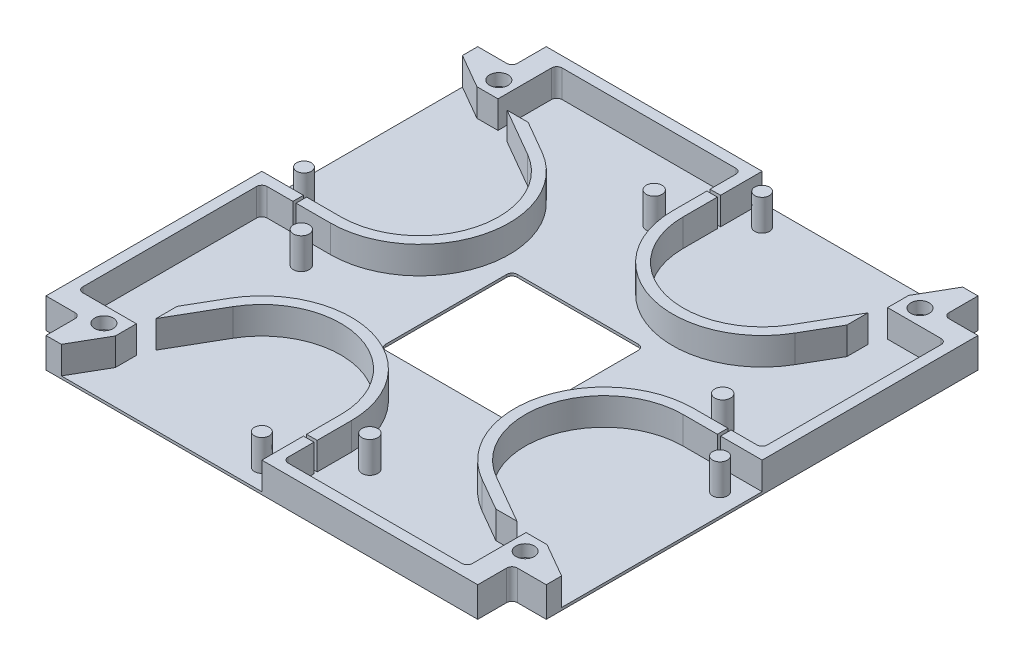
SolidWorks part; units mm, degrees
material "7075-T6 (SN)"
ref_plane "Front Plane" through (0, 0, 0) normal (0, 0, 1) x (1, 0, 0)
ref_plane "Top Plane" through (0, 0, 0) normal (0, 1, 0) x (1, 0, 0)
ref_plane "Right Plane" through (0, 0, 0) normal (1, 0, 0) x (0, 0, -1)
sketch "Sketch1" plane through (0, 0, 0) normal (0, 1, 0) x (1, 0, 0)
  line L0 (0, 0) -> (0, 6.51)
  line L21 (0, 6.51) -> (82, 6.51)
  line L22 (82, 6.51) -> (82, 0)
  line L23 (82, 0) -> (88.51, 0)
  line L24 (88.51, 0) -> (88.51, -82)
  line L25 (88.51, -82) -> (82, -82)
  line L26 (82, -82) -> (82, -88.51)
  line L27 (82, -88.51) -> (0, -88.51)
  line L28 (0, -88.51) -> (0, -82)
  line L29 (0, -82) -> (-6.51, -82)
  line L30 (-6.51, -82) -> (-6.51, 0)
  line L31 (-6.51, 0) -> (0, 0)
  dimension "D1" = 82
  dimension "D2" = 6.51
extrude "Boss-Extrude1" add sketch "Sketch1" along normal blind 0.5
sketch "Sketch2" plane through (0, 0.5, 0) normal (0, 1, 0) x (1, 0, 0)
  line L0 (-6.51, 0) -> (-6.51, -82) construction
  line L1 (0, 6.51) -> (41, 6.51)
  line L2 (0, 6.51) -> (0, 4.51)
  line L3 (0, 4.51) -> (41, 4.51)
  line L4 (41, 6.51) -> (41, 4.51)
  line L5 (88.51, 0) -> (86.51, 0)
  line L6 (88.51, 0) -> (88.51, -41)
  line L7 (88.51, -41) -> (86.51, -41)
  line L8 (86.51, 0) -> (86.51, -41)
  line L9 (82, -88.51) -> (41, -88.51)
  line L10 (82, -88.51) -> (82, -86.51)
  line L11 (82, -86.51) -> (41, -86.51)
  line L12 (41, -88.51) -> (41, -86.51)
  line L13 (-6.51, -82) -> (-4.51, -82)
  line L14 (-6.51, -82) -> (-6.51, -41)
  line L15 (-6.51, -41) -> (-4.51, -41)
  line L16 (-4.51, -82) -> (-4.51, -41)
  line L17 (-6.51, -82) -> (0, -82) construction
  line L18 (41, -8.49) -> (41, 24.5303) construction
  line L19 (56, 6.51) -> (0, 6.51) construction
  line L20 (82, 6.51) -> (0, 6.51) construction
  line L21 (79.094, 6.51) -> (75.3355, 0)
  line L22 (79.094, 6.51) -> (82, 6.51)
  line L23 (82, 6.51) -> (82, 0)
  line L24 (82, 0) -> (86.51, 0)
  line L25 (41, 4.51) -> (41, -8.49)
  line L26 (86.51, -4) -> (75.3355, -4)
  line L27 (39, 4.51) -> (39, -8.49)
  line L28 (72.9929, -8) -> (73.0261, -8)
  line L29 (74.3355, -10.7321) -> (70.7224, -16.99)
  line L31 (75.3355, -4) -> (75.3355, 0)
  line L32 (74.3355, -6.7321) -> (74.3355, -10.7321)
  line L33 (74.3355, -6.7321) -> (68.9904, -15.99)
  circle A0 centre (56, -8.49) radius 15
  circle A1 centre (56, -8.49) radius 17 construction
  arc A2 (70.7224, -16.99) -> (39, -8.49) centre (56, -8.49) cw
  line M24 (88.51, -82) -> (88.51, 0)
  line M25 (88.51, 0) -> (82, 0)
  line M26 (82, 0) -> (82, 6.51)
  line M27 (82, 6.51) -> (0, 6.51)
  line M28 (0, 6.51) -> (0, 0)
  dimension "D3" = 30
  dimension "D6" = 34
  dimension "D1" = 41
  dimension "D2" = 2
  dimension "D7" = 4
  dimension "D8" = 4
  dimension "D5" = 0
  dimension "D9" = 1
  dimension "D4" = 30
  dimension "D10" = 6.6645
  dimension "D11" = 30
  dimension "D12" = 4
extrude "Boss-Extrude2" add sketch "Sketch2" along normal blind 5.2 contours L4 L3 M27 M28 | A2 L28 A0 L25 L3 L27 | L8 L7 M25 M24 | L26 L8 M25 M26 M27 region at (80.332, 0.5, 0.0167) region at (20.5, 0.5, -5.51) region at (40.5365, 0.5, 1.99) region at (87.51, 0.5, 20.5)
sketch "Sketch3" [suppressed] plane through (0, 0.5, 0) normal (0, 1, 0) x (1, 0, 0)
  line L0 (35.5217, -6.4679) -> (39.51, -26.4679)
  line L1 (39.51, -26.4679) -> (39.51, -29.4679)
  line L2 (39.51, -29.4679) -> (79.51, -29.4679)
  line L3 (79.51, -29.4679) -> (79.51, -26.4679)
  line L4 (79.51, -26.4679) -> (83.4983, -6.4679)
  line L6 (35.5217, -6.4679) -> (39.5217, -6.4679)
  line L7 (83.4983, -6.4679) -> (79.4983, -6.4679)
  line L9 (89.51, -41) -> (89.51, 0) construction
  arc A0 (79.4983, -6.4679) -> (39.5217, -6.4679) centre (59.51, -5.7836) cw
  circle A1 centre (58.485, 0) radius 15 construction
  dimension "D3" = 20
  dimension "D7" = 30
  dimension "D1" = 3
  dimension "D2" = 4
  dimension "D4" = 20
  dimension "D5" = 40
  dimension "D6" = 10
extrude "Boss-Extrude3" [suppressed] add sketch "Sketch3" along normal blind 6
ref_plane "Plane1" through (41, 0, 41) normal (0.7071, 0, 0.7071) x (0.7071, 0, -0.7071)
ref_plane "Plane2" through (0, 0, 0) normal (0.7071, 0, -0.7071) x (-0.7071, 0, -0.7071)
ref_axis "Axis1" through (41, -0.325, 41) along (0, 1, 0)
pattern_circular "CirPattern1" count 4 every 90 about axis through (41, -0.325, 41) along (0, 1, 0) of "Boss-Extrude2"
sketch "Sketch4" plane through (0, 0, 0) normal (0, -1, 0) x (1, 0, 0)
  line L0 (78, -6.51) -> (78, -0.51) construction
  line L1 (82, -6.51) -> (0, -6.51) construction
  line L2 (82, 0) -> (82, -6.51) construction
  line L3 (88.51, 78) -> (82.51, 78) construction
  line L4 (88.51, 82) -> (88.51, 0) construction
  line L5 (4, 88.51) -> (4, 82.51) construction
  line L6 (0, 88.51) -> (82, 88.51) construction
  line L7 (-6.51, 4) -> (-0.51, 4) construction
  line L8 (-6.51, 0) -> (-6.51, 82) construction
  line L10 (82, 82) -> (88.51, 82) construction
  line L11 (0, 82) -> (0, 88.51) construction
  line L12 (0, 0) -> (-6.51, 0) construction
  point P7 (78, -0.51)
  dimension "D1" = 6
  dimension "D2" = 4
  dimension "D3" = 4
  dimension "D4" = 4
  dimension "D5" = 4
  dimension "D6" = 6
  dimension "D7" = 6
  dimension "D8" = 6
sketch "Sketch8" plane through (0, 0.5, 0) normal (0, 1, 0) x (1, 0, 0)
  line L0 (2.906, -88.51) -> (41, -88.51) construction
  line L1 (41, -88.51) -> (41, -73.51) construction
  circle A0 centre (37, -84.51) radius 1.4
  dimension "D1" = 2.8
  dimension "D2" = 4
  dimension "D3" = 4
extrude "Boss-Extrude4" add sketch "Sketch8" along normal blind 5.9
pattern_circular "CirPattern2" count 4 every 90 about axis through (41, -0.325, 41) along (0, 1, 0) of "Boss-Extrude4"
fillet "Fillet1" radius 1 8 edges at (-4.51, 3.1, 78) (-4.51, 3.1, 43) (4, 3.1, -4.51) (39, 3.1, -4.51) (86.51, 3.1, 4) (86.51, 3.1, 39) (78, 3.1, 86.51) (43, 3.1, 86.51)
sketch "Sketch11" plane through (0, 0.5, 0) normal (0, 1, 0) x (1, 0, 0)
  line L0 (53.5, -53.5) -> (53.5, -28.5)
  line L1 (53.5, -28.5) -> (28.5, -28.5)
  line L2 (28.5, -28.5) -> (28.5, -53.5)
  line L3 (28.5, -53.5) -> (53.5, -53.5)
  line L5 (79.094, 6.51) -> (41, 6.51) construction
  line L6 (-6.51, -2.906) -> (-6.51, -41) construction
  dimension "D1" = 25
  dimension "D2" = 25
  dimension "D3" = 35.01
  dimension "D4" = 35.01
extrude "Cut-Extrude2" cut sketch "Sketch11" against normal through all
sketch "Sketch14" plane through (0, 6.4, 0) normal (0, 1, 0) x (1, 0, 0)
  point P0 (37, -84.51)
sketch "Sketch15" plane through (0, 5.7, 0) normal (0, 1, 0) x (1, 0, 0)
  line L0 (82, -82) -> (88.51, -82) construction
  line L2 (78, -85.51) -> (78, -75.3355) construction
  circle A0 centre (81, -78.5) radius 0.9
  circle A1 centre (78.5, -1) radius 0.9
  circle A2 centre (1, -3.5) radius 0.9
  circle A3 centre (3.5, -81) radius 0.9
  point P0 (1, -3.5)
  point P1 (1, -3.5)
  point P2 (3.5, -81)
  point P3 (81, -78.5)
  point P4 (78.5, -1)
  point P5 (3.5, -81)
  dimension "D3" = 1.8
  dimension "D4" = 1.8
  dimension "D5" = 1.8
  dimension "D6" = 1.8
  dimension "D1" = 3.5
  dimension "D2" = 3
extrude "Cut-Extrude3" cut sketch "Sketch15" against normal through all
sketch "Sketch16" plane through (0, 5.7, 0) normal (0, 1, 0) x (1, 0, 0)
  circle A0 centre (78.5, -1) radius 1.75
  circle A1 centre (81, -78.5) radius 1.75
  circle A2 centre (3.5, -81) radius 1.75
  circle A3 centre (1, -3.5) radius 1.75
  dimension "D1" = 3.5
  dimension "D2" = 3.5
  dimension "D3" = 3.5
  dimension "D4" = 3.5
extrude "Cut-Extrude4" cut sketch "Sketch16" against normal blind 2.3
hole_wizard "CBORE for M1.6 SHCS2" positions "3DSketch2" profile "Sketch18" counterbore size "M1.6" standard "ANSI Metric" end condition through all
sketch3d "3DSketch2"
  line L0 (81, 0, 78.5) -> (81, 3.4, 78.5) construction
  line L1 (78.5, 0, 1) -> (78.5, 3.4, 1) construction
  line L2 (1, 0, 3.5) -> (1, 3.4, 3.5) construction
  line L3 (3.5, 0, 81) -> (3.5, 3.4, 81) construction
  point P0 (81, 0, 78.5)
  point P4 (78.5, 0, 1)
  point P8 (1, 0, 3.5)
  point P12 (3.5, 0, 81)
sketch "Sketch18" plane through (81, 0, 78.5) normal (1, 0, 0) x (0, 0, -1)
  line L0 (0, 0) -> (0, 6.4)
  line L1 (0, 6.4) -> (0.9, 6.4)
  line L3 (0.9, 6.4) -> (0.9, 1.6)
  line L4 (0.9, 1.6) -> (1.75, 1.6)
  line L5 (1.75, 1.6) -> (1.75, 0)
  line L7 (1.75, 0) -> (0, 0)
  line L11 (0, -6.35) -> (0, 107.95) construction
  dimension "Thru Hole Dia." = 1.8
  dimension "Thru Hole Depth" = 6.4
  dimension "C'Bore Dia." = 3.5
  dimension "C'Bore Depth" = 1.6
sketch "Sketch20" plane through (0, 5.7, 0) normal (0, 1, 0) x (1, 0, 0)
  line L0 (80.61, -39) -> (80.61, -41)
  line L1 (85.51, -39) -> (73.51, -39) construction
  line L2 (88.51, -41) -> (73.51, -41) construction
  line L3 (80.61, -41) -> (80.01, -41)
  line L4 (80.01, -41) -> (80.01, -39)
  line L5 (80.01, -39) -> (80.61, -39)
  circle A0 centre (84.51, -45) radius 1.4 construction
  dimension "D1" = 3.9
  dimension "D2" = 4.5
sketch "Sketch24" plane through (0, 0.5, 0) normal (0, 1, 0) x (1, 0, 0)
  point P0 (41, -41)
  dimension "D1" = 41
  dimension "D2" = 41
extrude "Cut-Extrude6" cut sketch "Sketch20" against normal up to surface (5.2 mm away) up to face at (41, 0.5, 41)
pattern_circular "CirPattern3" count 4 over 360 about axis through (41, -0.325, 41) along (0, 1, 0) of "Cut-Extrude6"
fillet "Fillet2" radius 1 4 edges at (0, 2.85, 0) (82, 2.85, 0) (82, 2.85, 82) (0, 2.85, 82)
sketch "Sketch25" plane through (0, 0.5, 0) normal (0, 1, 0) x (1, 0, 0)
  line L1 (79.094, 6.51) -> (41, 6.51) construction
  line L2 (88.51, -41) -> (88.51, 0) construction
  circle A0 centre (74.51, -34.49) radius 1.5
  point P0 (74.51, -34.49)
  dimension "D2" = 3
  dimension "D1" = 41
  dimension "D3" = 14
extrude "Boss-Extrude5" add sketch "Sketch25" along normal blind 5.9
pattern_circular "CirPattern4" count 4 over 360 about axis through (41, -0.325, 41) along (0, 1, 0) of "Boss-Extrude5"
fillet "Fillet3" radius 1 4 edges at (28.5, 0.25, 28.5) (28.5, 0.25, 53.5) (53.5, 0.25, 53.5) (53.5, 0.25, 28.5)
equation "\"D6@Sketch2\"=\"D3@Sketch2\"+4"
equation "\"D3@Sketch4\"=\"D2@Sketch4\""
equation "\"D4@Sketch4\"=\"D3@Sketch4\""
equation "\"D5@Sketch4\"=\"D4@Sketch4\""
equation "\"D6@Sketch4\"=\"D1@Sketch4\""
equation "\"D7@Sketch4\"=\"D6@Sketch4\""
equation "\"D8@Sketch4\"=\"D7@Sketch4\""
